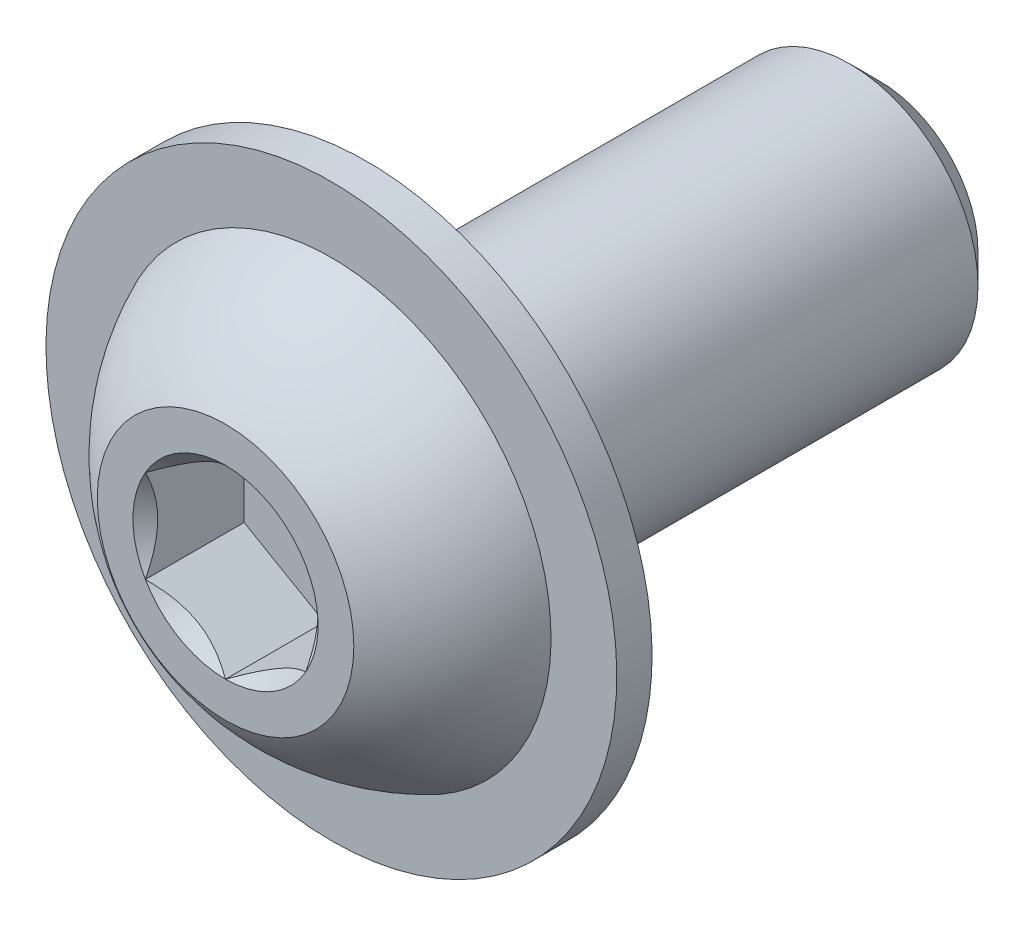
SolidWorks part; units mm, degrees
material "Alloy Steel"
ref_plane "Front" through (0, 0, 0) normal (0, 0, 1) x (1, 0, 0)
ref_plane "Top" through (0, 0, 0) normal (0, 1, 0) x (1, 0, 0)
ref_plane "Right" through (0, 0, 0) normal (1, 0, 0) x (0, 0, -1)
sketch "Sketch1" plane through (0, 0, 0) normal (1, 0, 0) x (0, 0, -1)
  line L2 (-5.8, 4) -> (10.2, 4)
  line L3 (10.2, 4) -> (10.2, 0)
  line L4 (10.2, -4) -> (8.95, -4) construction
  line L6 (-6.9, 6.85) -> (-5.8, 6.85) construction
  line L7 (10.2, 4) -> (10.2, -4) construction
  line L8 (-10.2, 0) -> (10.2, 0) construction
  line L9 (-5.8, 6.85) -> (-5.8, -6.85) construction
  line L11 (-5.8, 4) -> (-5.8, 0)
  line L13 (-10.2, 2.5) -> (-10.2, -2.5) construction
  line L14 (-10.2, 2.5) -> (-10.2, 4) construction
  line L15 (-6.9, 6.85) -> (-6.9, 8.9) construction
  line L16 (-6.9, 8.9) -> (-5.8, 8.9) construction
  line L17 (-5.8, 8.9) -> (-5.8, 6.85) construction
  line L18 (-5.8, 8.9) -> (-5.8, -8.9) construction
  arc A3 (-10.2, 4) -> (-6.9, 6.85) centre (-3.8648, 0) cw construction
  point P16 (5.825, -4)
  point P24 (0, 0)
  dimension "Thread OD" = 8
  dimension "D1" = 1.1
  dimension "Head Height" = 4.4
  dimension "Head Diameter" = 13.7
  dimension "Length" = 16
  dimension "Drive Size" = 5
  dimension "Flange Diameter" = 17.8
  dimension "D2" = 4.375
  dimension "Thread Pitch" = 1.25
sketch "Sketch13" plane through (0, 0, 0) normal (1, 0, 0) x (0, 0, -1)
  line L1 (-5.8, 4) -> (10.2, 4)
  line L2 (-5.8, 4) -> (-5.8, 0)
  line L3 (-5.8, 0) -> (10.2, 0)
  line L4 (10.2, 4) -> (10.2, 0)
revolve "Revolve1" add sketch "Sketch13" angle 360 about L8
chamfer "Chamfer1" distance 0.9375 angle 45 1 edges at (4, 0, -10.2)
sketch "Sketch7" plane through (0, 0, 0) normal (1, 0, 0) x (0, 0, -1)
  line L0 (-5.8, 6.85) -> (-5.8, -6.85) construction
  line L1 (-5.8, 6.85) -> (-5.8, 0)
  line L2 (-6.9, 6.85) -> (-6.9, 8.9)
  line L3 (-6.9, 8.9) -> (-5.8, 8.9)
  line L4 (-5.8, 8.9) -> (-5.8, 6.85)
  line L6 (-6.9, 6.85) -> (-5.8, 6.85) construction
  line L8 (-10.2, 0) -> (10.2, 0) construction
  line L12 (-6.9, 6.85) -> (-5.8, 6.85) construction
  line L13 (-10.2, 0) -> (-5.8, 0)
  line L14 (-10.2, 2.5) -> (-10.2, -2.5) construction
  line L16 (-10.2, 4) -> (-10.2, 0)
  arc A2 (-6.9, 6.85) -> (-10.2, 4) centre (-3.8648, 0) ccw construction
  arc A3 (-6.9, 6.85) -> (-10.2, 4) centre (-3.8648, 0) ccw
revolve "Revolve2" add sketch "Sketch7" angle 360 mid plane about L13
sketch "Sketch5" plane through (0, 0, 10.2) normal (0, 0, 1) x (1, 0, 0)
  line L1 (2.5, -1.4434) -> (2.5, 1.4434)
  line L2 (2.5, 1.4434) -> (0, 2.8868)
  line L3 (0, 2.8868) -> (-2.5, 1.4434)
  line L4 (-2.5, 1.4434) -> (-2.5, -1.4434)
  line L5 (-2.5, -1.4434) -> (0, -2.8868)
  line L6 (0, -2.8868) -> (2.5, -1.4434)
  circle A0 centre (0, 0) radius 2.5 construction
extrude "Cut-Extrude2" cut sketch "Sketch5" against normal blind 3.08
sketch "Sketch6" plane through (0, 0, 10.2) normal (0, 0, 1) x (1, 0, 0)
  circle A0 centre (0, 0) radius 2.8868
extrude "Cut-Extrude3" cut sketch "Sketch6" against normal blind 3.08 draft 45
split "Split1" [suppressed] bodies to split 113
sketch "Sketch14" [suppressed] plane through (0, 0, -10.2) normal (0, 0, -1) x (-1, 0, 0)
  circle A0 centre (0, 0) radius 4 construction
  circle A1 centre (0, 0) radius 4
curve "Helix/Spiral1" [suppressed] pitch 1.25 height 17.25 turns 13.8
sketch "Sketch16" [suppressed] plane through (0, 0, 0) normal (1, 0, 0) x (0, 0, -1)
  line L0 (11.3719, 4.1353) -> (10.1219, 4.1353) construction
  line L1 (10.1219, 4.1353) -> (10.7469, 3.0528) construction
  line L2 (10.7469, 3.0528) -> (11.3719, 4.1353) construction
  line L3 (11.2937, 4) -> (10.2, 4) construction
  line L4 (10.7469, 4.1353) -> (10.7469, 4) construction
  line L5 (11.3328, 4.0677) -> (10.1609, 4.0677) construction
  line L6 (10.825, 3.1881) -> (10.6687, 3.1881) construction
  line L7 (10.7469, 3.1881) -> (10.7469, 3.0528) construction
  line L8 (10.6687, 3.1881) -> (10.1609, 4.0677)
  line L9 (10.1609, 4.0677) -> (11.3328, 4.0677)
  line L10 (11.3328, 4.0677) -> (10.825, 3.1881)
  line L11 (10.825, 3.1881) -> (10.6687, 3.1881)
  point P11 (10.7469, 4.0677)
  dimension "D1" = 1.25
  dimension "D2" = 0.1562
sweep "Cut-Sweep1" [suppressed] cut profiles "Sketch16" path "Helix/Spiral1"
sketch "Sketch17" [suppressed] plane through (0, 0, 5.8) normal (0, 0, -1) x (-1, 0, 0)
  circle A1 centre (0, 0) radius 4
  circle A2 centre (0, 0) radius 4
  dimension "D1" = 0
extrude "Boss-Extrude1" [suppressed] add sketch "Sketch17" along normal up to next draft 20
equation "\"D3@Helix/Spiral1\" = \"Length@Sketch1\" + \"D4@Helix/Spiral1\""
equation "\"D1@Chamfer1\" = \"D4@Helix/Spiral1\" * .75"
equation "\"D1@Cut-Extrude2\" = \"Head Height@Sketch1\" * .7"
equation "\"D1@Sketch1\" = \"Head Height@Sketch1\" * .25"
equation "\"D1@Cut-Extrude3\" = \"D1@Cut-Extrude2\""
equation "\"D2@Sketch1\"=\"D4@Helix/Spiral1\"*3.5"
equation "\"D4@Helix/Spiral1\"=\"Thread Pitch@Sketch1\""
equation "\"D1@Sketch16\"=\"Thread Pitch@Sketch1\""
equation "\"D2@Sketch16\"=\"D1@Sketch16\"/8"
